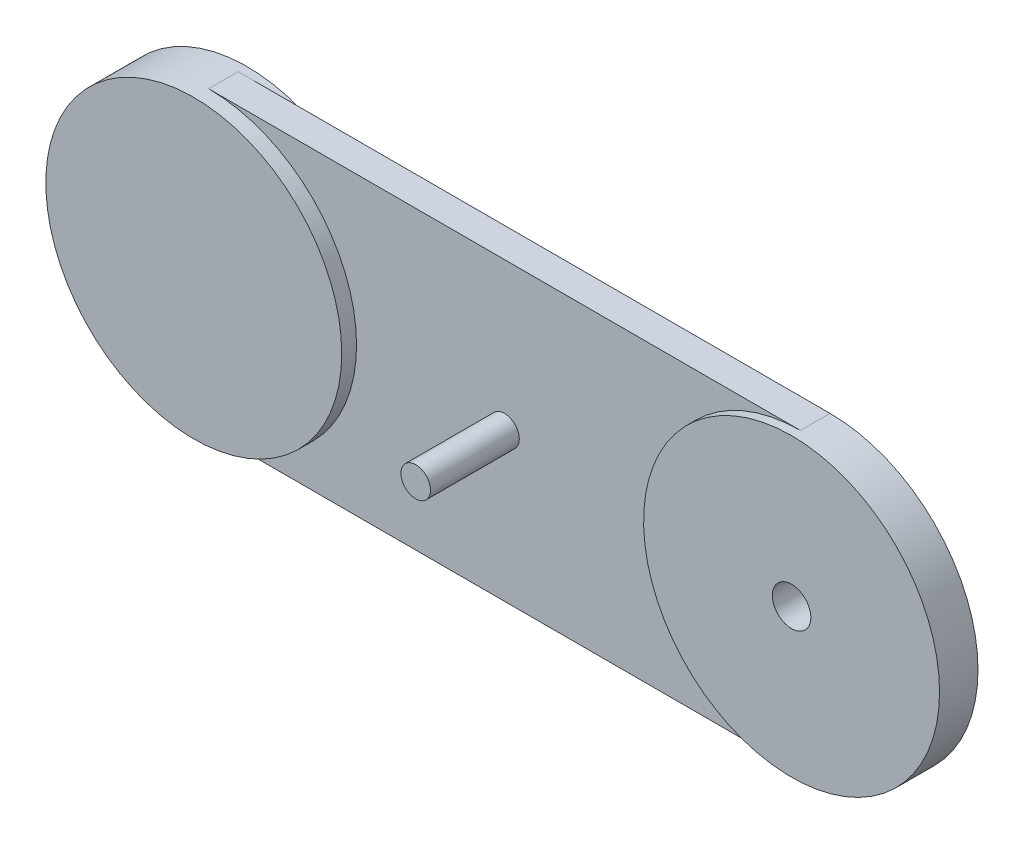
SolidWorks part; units mm, degrees
material "3003 合金"
ref_plane "前视基准面" through (0, 0, 0) normal (0, 0, 1) x (1, 0, 0)
ref_plane "上视基准面" through (0, 0, 0) normal (0, 1, 0) x (1, 0, 0)
ref_plane "右视基准面" through (0, 0, 0) normal (1, 0, 0) x (0, 0, -1)
sketch "草图1" plane through (0, 0, 0) normal (0, 0, 1) x (1, 0, 0)
  line L0 (0, 100) -> (-200, 0)
  line L5 (0, 0) -> (-200, 0)
  line L6 (0, 0) -> (0, 100)
  line L7 (0, 100) -> (-200, 100)
  line L8 (-200, 0) -> (-200, 100)
  line L9 (-200, 100) -> (0, 0)
  circle A6 centre (0, 50) radius 50
  circle A7 centre (0, 50) radius 25
  circle A8 centre (-200, 50) radius 50
  circle A9 centre (-200, 50) radius 25
  circle A12 centre (-100, 50) radius 5
  circle A13 centre (0, 50) radius 6.5
  dimension "D1" = 100
  dimension "D2" = 200
  dimension "D3" = 50
  dimension "D4" = 50
  dimension "D5" = 10
  dimension "D6" = 13
extrude "凸台-拉伸18" add sketch "草图1" along normal blind 13 contours A8 | A6
extrude "凸台-拉伸21" add sketch "草图1<28>" along normal blind 10 contours L5 L8 L7 L6
sketch "草图1<28>" plane through (0, 0, 0) normal (0, 0, 1) x (1, 0, 0) same geometry as "草图1"
extrude "凸台-拉伸22" add sketch "草图1<30>" along normal blind 40 contours A12
sketch "草图1<30>" plane through (0, 0, 0) normal (0, 0, 1) x (1, 0, 0) same geometry as "草图1"
extrude "切除-拉伸2" cut sketch "草图1<31>" along normal blind 41 contours A8
sketch "草图1<31>" plane through (0, 0, 0) normal (0, 0, 1) x (1, 0, 0) same geometry as "草图1"
extrude "凸台-拉伸23" add sketch "草图1<32>" along normal blind 15 and the other way blind 3 contours A8
sketch "草图1<32>" plane through (0, 0, 0) normal (0, 0, 1) x (1, 0, 0) same geometry as "草图1"
extrude "切除-拉伸3" cut sketch "草图1<33>" along normal blind 242.8 contours A13
sketch "草图1<33>" plane through (0, 0, 0) normal (0, 0, 1) x (1, 0, 0) same geometry as "草图1"
